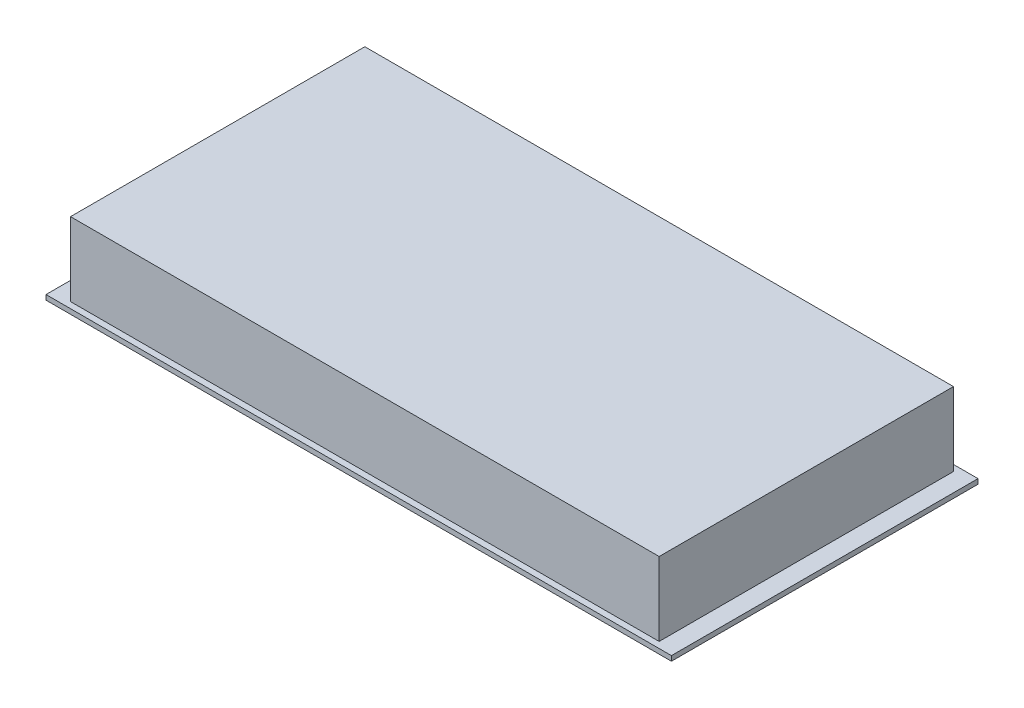
SolidWorks part; units mm, degrees
ref_plane "Front" through (0, 0, 0) normal (0, 0, 1) x (1, 0, 0)
ref_plane "Top" through (0, 0, 0) normal (0, 1, 0) x (1, 0, 0)
ref_plane "Right" through (0, 0, 0) normal (1, 0, 0) x (0, 0, -1)
sketch "Sketch1" plane through (0, 0, 0) normal (0, 1, 0) x (1, 0, 0)
  line L1 (-152.4, 76.2) -> (152.4, 76.2)
  line L2 (-152.4, 76.2) -> (-152.4, -76.2)
  line L3 (-152.4, -76.2) -> (152.4, -76.2)
  line L4 (152.4, 76.2) -> (152.4, -76.2)
  line L5 (-152.4, 76.2) -> (152.4, -76.2) construction
  line L6 (-152.4, -76.2) -> (152.4, 76.2) construction
  point P0 (0, 0)
  dimension "D1" = 304.8
  dimension "D2" = 152.4
extrude "Boss-Extrude1" add sketch "Sketch1" along normal blind 38.1
sketch "Sketch2" plane through (0, 0, 0) normal (0, -1, 0) x (1, 0, 0)
  line L0 (152.4, 76.2) -> (152.4, -76.2) construction
  line L1 (-161.925, 79.375) -> (161.925, 79.375)
  line L2 (-161.925, 79.375) -> (-161.925, -79.375)
  line L3 (-161.925, -79.375) -> (161.925, -79.375)
  line L4 (161.925, 79.375) -> (161.925, -79.375)
  line L5 (-161.925, 79.375) -> (161.925, -79.375) construction
  line L6 (-161.925, -79.375) -> (161.925, 79.375) construction
  line L7 (-152.4, 76.2) -> (152.4, 76.2) construction
  point P0 (0, 0)
  dimension "D1" = 9.525
  dimension "D2" = 3.175
extrude "Boss-Extrude2" add sketch "Sketch2" along normal blind 2.54
